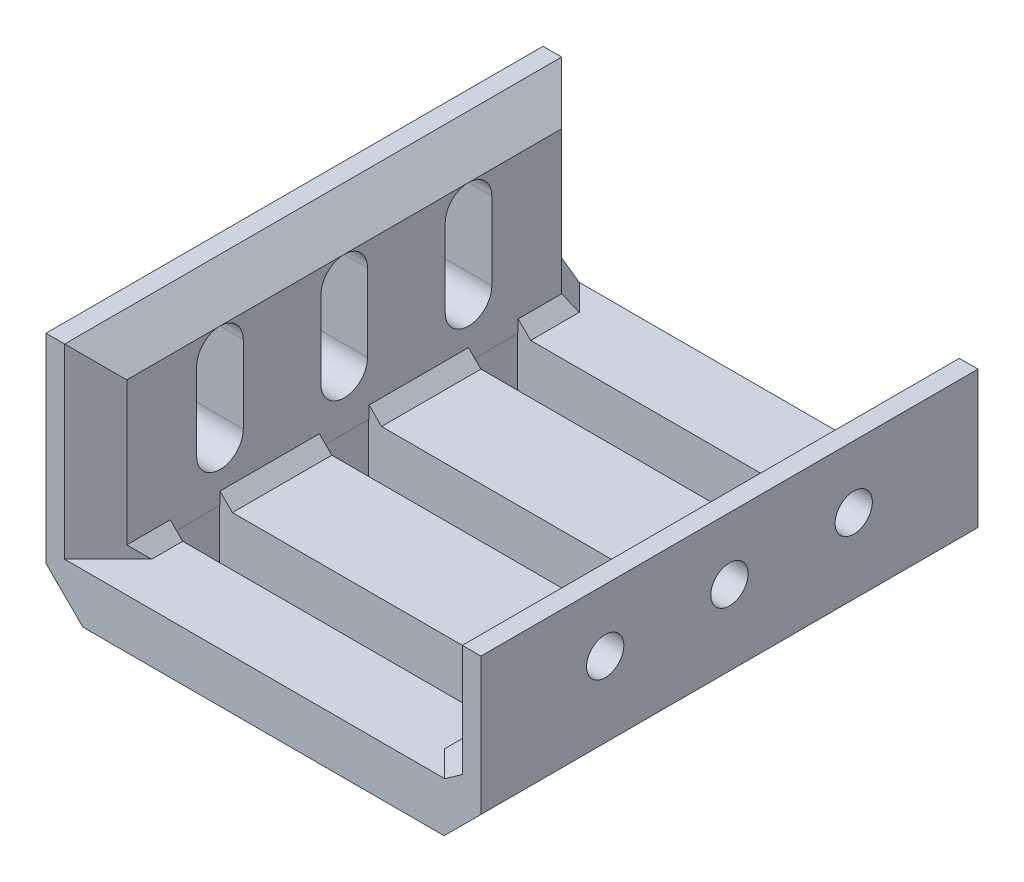
SolidWorks part; units mm, degrees
material "Plain Carbon Steel"
ref_plane "Front Plane" through (0, 0, 0) normal (0, 0, 1) x (1, 0, 0)
ref_plane "Top Plane" through (0, 0, 0) normal (0, 1, 0) x (1, 0, 0)
ref_plane "Right Plane" through (0, 0, 0) normal (1, 0, 0) x (0, 0, -1)
sketch "Sketch1" plane through (0, 0, 0) normal (0, 1, 0) x (1, 0, 0)
  line L1 (22.225, 25.4) -> (-22.225, 25.4)
  line L2 (22.225, 25.4) -> (22.225, -25.4)
  line L3 (22.225, -25.4) -> (-22.225, -25.4)
  line L4 (-22.225, 25.4) -> (-22.225, -25.4)
  line L5 (22.225, 25.4) -> (-22.225, -25.4) construction
  line L6 (22.225, -25.4) -> (-22.225, 25.4) construction
  point P0 (0, 0)
  dimension "D1" = 44.45
  dimension "D2" = 50.8
extrude "Boss-Extrude1" add sketch "Sketch1" along normal blind 6.35
sketch "Sketch2" plane through (0, 0, 0) normal (0, 1, 0) x (1, 0, 0)
  line L1 (-22.225, 25.4) -> (-17.145, 25.4)
  line L2 (-22.225, 25.4) -> (-22.225, -25.4)
  line L3 (-22.225, -25.4) -> (-17.145, -25.4)
  line L4 (-17.145, 25.4) -> (-17.145, -25.4)
  line L5 (22.225, 25.4) -> (-22.225, 25.4) construction
  dimension "D1" = 5.08
extrude "Boss-Extrude2" add sketch "Sketch2" along normal blind 25.4
sketch "Sketch3" plane through (0, 0, 0) normal (0, 1, 0) x (1, 0, 0)
  line L1 (22.225, 25.4) -> (17.145, 25.4)
  line L2 (22.225, 25.4) -> (22.225, -25.4)
  line L3 (22.225, -25.4) -> (17.145, -25.4)
  line L4 (17.145, 25.4) -> (17.145, -25.4)
  line L7 (-22.225, -25.4) -> (22.225, -25.4) construction
  dimension "D1" = 5.08
extrude "Boss-Extrude3" add sketch "Sketch3" along normal blind 19.05
sketch "Sketch4" plane through (-17.145, 0, 0) normal (1, 0, 0) x (0, 0, -1)
  line L0 (-25.4, 25.4) -> (-25.4, 6.35) construction
  line L1 (0, 11.9063) -> (0, 19.8437) construction
  line L2 (-2.3813, 11.9063) -> (-2.3813, 19.8437)
  line L3 (2.3813, 11.9063) -> (2.3813, 19.8437)
  line L6 (-25.4, 25.4) -> (25.4, 25.4) construction
  line L8 (25.4, 25.4) -> (-25.4, 25.4) construction
  arc A0 (-2.3813, 11.9063) -> (2.3813, 11.9063) centre (0, 11.9063) ccw
  arc A1 (2.3813, 19.8437) -> (-2.3813, 19.8437) centre (0, 19.8437) ccw
  point P4 (0, 25.4)
  point P5 (0, 15.875)
  point P12 (-25.4, 15.875)
  point P13 (0, 25.4)
  dimension "D1" = 3.175
  dimension "D2" = 4.7625
extrude "Cut-Extrude1" cut sketch "Sketch4" against normal up to next
sketch "Sketch5" plane through (17.145, 0, 0) normal (-1, 0, 0) x (0, 0, 1)
  line L0 (-25.4, 19.05) -> (-25.4, 6.35) construction
  line L1 (-25.4, 19.05) -> (25.4, 19.05) construction
  circle A0 centre (0, 12.7) radius 1.905
  point P2 (-25.4, 12.7)
  point P7 (0, 19.05)
  dimension "D1" = 3.81
extrude "Cut-Extrude2" cut sketch "Sketch5" against normal up to next
pattern_linear "LPattern1" count 2 spacing 12.7 along (0, 0, 1) count 2 spacing 12.7 along (0, 0, -1) of "Cut-Extrude1", "Cut-Extrude2"
chamfer "Chamfer3" distance 5.0289 angle 45 2 edges at (-22.225, 0, 0) (22.225, 0, 0)
chamfer "Chamfer1" distance 3.175 angle 45 6 edges at (-17.145, 15.875, -25.4) (17.145, 19.05, 0) (-17.145, 15.875, 25.4) (-17.145, 25.4, 0) (17.145, 12.7, -25.4) (17.145, 12.7, 25.4)
sketch "Sketch6" plane through (0, 6.35, 0) normal (0, 1, 0) x (1, 0, 0)
  line L0 (17.1961, 25.4) -> (-17.1961, 25.4) construction
  line L1 (17.1961, 2.54) -> (-17.1961, 2.54)
  line L2 (17.1961, 2.54) -> (17.1961, -2.54)
  line L3 (17.1961, -2.54) -> (-17.1961, -2.54)
  line L4 (-17.1961, 2.54) -> (-17.1961, -2.54)
  line L5 (0, 2.54) -> (0, -2.54) construction
  line L7 (17.1961, 25.4) -> (17.1961, -25.4) construction
  point P6 (0, -2.54)
  point P11 (0, 2.54)
  point P12 (0, 0)
  dimension "D1" = 5.08
extrude "Cut-Extrude3" cut sketch "Sketch6" against normal up to next
pattern_linear "LPattern2" count 2 spacing 15.24 along (0, 0, 1) count 2 spacing 15.24 along (0, 0, -1) of "Cut-Extrude3" pattern seed only yes
chamfer "Chamfer4" distance 1.27 angle 45 18 edges at (-18.7325, 6.35, -23.8125) (18.7325, 6.35, 23.8125) (17.145, 6.35, -20.0025) (17.145, 6.35, -7.62) (17.145, 6.35, 7.62) (-17.145, 6.35, 20.0025) (-17.145, 6.35, 7.62) (-17.145, 6.35, -7.62) (17.145, 6.35, 20.0025) (-17.145, 6.35, -20.0025) (0, 0, -25.4) (0, 0, -17.78) (0, 0, -12.7) (0, 0, -2.54) (0, 0, 2.54) (0, 0, 12.7) (0, 0, 17.78) (0, 0, 25.4)
